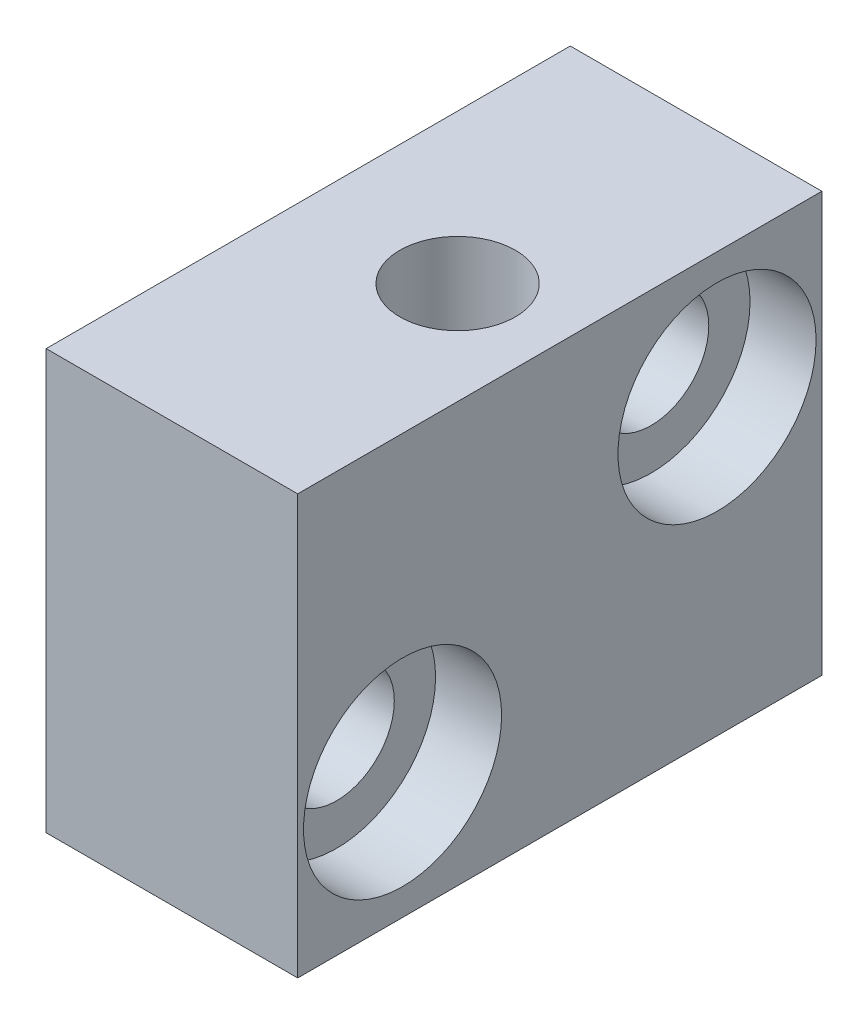
SolidWorks part; units mm, degrees
material "6061-T6 (SS)"
ref_plane "Front Plane" through (0, 0, 0) normal (1, 0, 0) x (0, 1, 0)
ref_plane "Top Plane" through (0, 0, 0) normal (0, 0, 1) x (0, 1, 0)
ref_plane "Right Plane" through (0, 0, 0) normal (0, 1, 0) x (-1, 0, 0)
sketch "Sketch1" plane through (0, 0, 0) normal (1, 0, 0) x (0, 1, 0)
  line L1 (6.35, -7.9375) -> (-6.35, -7.9375)
  line L2 (6.35, -7.9375) -> (6.35, 7.9375)
  line L3 (6.35, 7.9375) -> (-6.35, 7.9375)
  line L4 (-6.35, -7.9375) -> (-6.35, 7.9375)
  line L5 (6.35, -7.9375) -> (-6.35, 7.9375) construction
  line L6 (6.35, 7.9375) -> (-6.35, -7.9375) construction
  point P0 (0, 0)
  dimension "D1" = 15.875
  dimension "D2" = 12.7
extrude "Boss-Extrude1" add sketch "Sketch1" along normal blind 7.62
sketch "Sketch3" plane through (0, -6.35, 0) normal (0, -1, 0) x (1, 0, 0)
  line L10 (0, 7.9375) -> (0, -7.9375)
  line L11 (0, -7.9375) -> (7.62, -7.9375)
  line L12 (7.62, -7.9375) -> (7.62, 7.9375)
  line L13 (7.62, 7.9375) -> (0, 7.9375)
  line L14 (0, 7.9375) -> (0, -7.9375)
  line L15 (0, -7.9375) -> (7.62, -7.9375)
  line L16 (7.62, -7.9375) -> (7.62, 7.9375)
  line L17 (7.62, 7.9375) -> (0, 7.9375)
  circle A0 centre (4.525, 0) radius 1.75
  circle A1 centre (4.525, 0) radius 5 construction
  circle A2 centre (4.525, 0) radius 3 construction
  point P2 (9.525, 0)
  point P3 (2.775, 0)
  point P6 (-6.35, 0)
  dimension "D1" = 3.5
  dimension "D2" = 10
  dimension "D6" = 6
  dimension "D3" = 15.875
  dimension "D4" = 6.35
  dimension "D5" = 0
extrude "Cut-Extrude1" cut sketch "Sketch3" against normal blind 22.2885 contours A0 region at (4.525, -6.35, 0)
sketch "Sketch4" plane through (7.62, 0, 0) normal (1, 0, 0) x (0, 1, 0)
  line L0 (-6.35, 7.9375) -> (-6.35, -7.9375) construction
  line L1 (2.54, -4.7625) -> (-2.54, -4.7625) construction
  line L2 (2.54, -4.7625) -> (2.54, 4.7625) construction
  line L3 (2.54, 4.7625) -> (-2.54, 4.7625) construction
  line L4 (-2.54, -4.7625) -> (-2.54, 4.7625) construction
  line L5 (2.54, -4.7625) -> (-2.54, 4.7625) construction
  line L6 (2.54, 4.7625) -> (-2.54, -4.7625) construction
  line L7 (6.35, 7.9375) -> (-6.35, 7.9375) construction
  circle A5 centre (-2.54, 4.7625) radius 1.75
  circle A6 centre (2.54, -4.7625) radius 1.75
  point P0 (0, 0)
  dimension "D3" = 3.5
  dimension "D1" = 3.81
  dimension "D2" = 3.175
extrude "Cut-Extrude2" cut sketch "Sketch4" against normal blind 22.2885 contours A5 | A6 region at (7.62, -2.54, 4.7625) region at (7.62, 2.54, -4.7625)
sketch "Sketch5" plane through (7.62, 0, 0) normal (1, 0, 0) x (0, 1, 0)
  circle A0 centre (2.54, -4.7625) radius 1.75 construction
  circle A1 centre (-2.54, 4.7625) radius 1.75 construction
  circle A2 centre (2.54, -4.7625) radius 1.75 construction
  circle A3 centre (-2.54, 4.7625) radius 1.75 construction
  circle A4 centre (-2.54, 4.7625) radius 3
  circle A5 centre (2.54, -4.7625) radius 3
  dimension "D1" = 6
extrude "Cut-Extrude3" cut sketch "Sketch5" against normal blind 2
